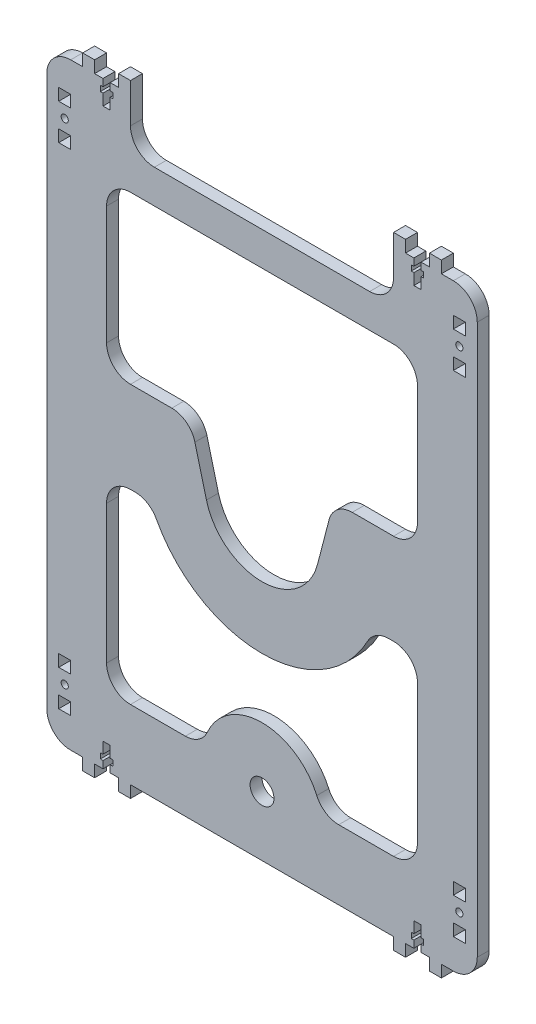
SolidWorks part; units mm, degrees
ref_plane "Front Plane" through (0, 0, 0) normal (0, 0, 1) x (1, 0, 0)
ref_plane "Top Plane" through (0, 0, 0) normal (0, 1, 0) x (1, 0, 0)
ref_plane "Right Plane" through (0, 0, 0) normal (1, 0, 0) x (0, 0, -1)
sketch "Sketch1" plane through (0, 0, 0) normal (0, 0, 1) x (1, 0, 0)
  line L0 (0, 0) -> (187.0096, 0) construction
  line L1 (-90, 125) -> (-55, 125) construction
  line L2 (-90, 125) -> (-90, -125)
  line L3 (-90, -125) -> (90, -125)
  line L4 (90, 125) -> (90, -125)
  line L5 (0, 0) -> (0, 134.5508) construction
  line L6 (-23.2273, -6.0409) -> (-30, 20)
  line L7 (-65, 89.5396) -> (65, 89.5396)
  line L8 (65, 89.5396) -> (65, 0) construction
  line L9 (65, 0) -> (-65, 0) construction
  line L10 (-65, 0) -> (-65, 89.5396) construction
  line L11 (-65, 0) -> (-20, 0) construction
  line L12 (20, 0) -> (65, 0) construction
  line L13 (82.5, 125) -> (82.5, -125) construction
  line L14 (0, 0) -> (0, -125) construction
  line L21 (-30, 20) -> (-65, 20)
  line L22 (-65, 20) -> (-65, 89.5396)
  line L23 (65, 20) -> (65, 89.5396)
  line L24 (30, 20) -> (65, 20)
  line L26 (-90, 125) -> (-55, 125)
  line L27 (23.2273, -6.0409) -> (30, 20)
  line L28 (-55, 125) -> (-55, 103.5988)
  line L29 (-55, 103.5988) -> (55, 103.5988)
  line L30 (55, 103.5988) -> (55, 125)
  line L31 (55, 125) -> (90, 125) construction
  line L32 (55, 125) -> (90, 125)
  line L33 (-46.616, -18.0816) -> (-65, -18.0816)
  line L34 (-65, -18.0816) -> (-65, -95.958)
  line L35 (-65, -95.958) -> (-24.6711, -95.958)
  line L36 (46.616, -18.0816) -> (65, -18.0816)
  line L37 (65, -18.0816) -> (65, -95.958)
  line L38 (65, -95.958) -> (24.6711, -95.958)
  circle A1 centre (0, -100) radius 5
  circle A2 centre (0, 0) radius 24 construction
  arc A3 (23.2273, -6.0409) -> (-23.2273, -6.0409) centre (0, 0) cw
  circle A4 centre (0, 0) radius 50 construction
  circle A5 centre (0, -100) radius 25 construction
  arc A6 (24.6711, -95.958) -> (-24.6711, -95.958) centre (0, -100) ccw
  arc A7 (-46.616, -18.0816) -> (46.616, -18.0816) centre (0, 0) ccw
  line B0 (82.5, 107.5) -> (82.5, 97.5) construction
  line B1 (80, 107.5) -> (80, 112.5)
  line B2 (80, 107.5) -> (85, 107.5)
  line B3 (85, 107.5) -> (85, 112.5)
  line B4 (80, 112.5) -> (85, 112.5)
  line B5 (80, 97.5) -> (80, 92.5)
  line B6 (80, 97.5) -> (85, 97.5)
  line B7 (85, 97.5) -> (85, 92.5)
  line B8 (80, 92.5) -> (85, 92.5)
  line B9 (82.5, 102.5) -> (75.5276, 102.5) construction
  circle B10 centre (82.5, 102.5) radius 1.5
  line B11 (82.5, -107.5) -> (82.5, -97.5) construction
  line B12 (80, -107.5) -> (80, -112.5)
  line B13 (80, -107.5) -> (85, -107.5)
  line B14 (85, -107.5) -> (85, -112.5)
  line B15 (80, -112.5) -> (85, -112.5)
  line B16 (80, -97.5) -> (80, -92.5)
  line B17 (80, -97.5) -> (85, -97.5)
  line B18 (85, -97.5) -> (85, -92.5)
  line B19 (80, -92.5) -> (85, -92.5)
  line B20 (82.5, -102.5) -> (75.5276, -102.5) construction
  circle B21 centre (82.5, -102.5) radius 1.5
  line B22 (-82.5, 107.5) -> (-82.5, 97.5) construction
  line B23 (-80, 107.5) -> (-80, 112.5)
  line B24 (-80, 107.5) -> (-85, 107.5)
  line B25 (-85, 107.5) -> (-85, 112.5)
  line B26 (-80, 112.5) -> (-85, 112.5)
  line B27 (-80, 97.5) -> (-80, 92.5)
  line B28 (-80, 97.5) -> (-85, 97.5)
  line B29 (-85, 97.5) -> (-85, 92.5)
  line B30 (-80, 92.5) -> (-85, 92.5)
  line B31 (-82.5, 102.5) -> (-75.5276, 102.5) construction
  circle B32 centre (-82.5, 102.5) radius 1.5
  line B33 (-82.5, -107.5) -> (-82.5, -97.5) construction
  line B34 (-80, -107.5) -> (-80, -112.5)
  line B35 (-80, -107.5) -> (-85, -107.5)
  line B36 (-85, -107.5) -> (-85, -112.5)
  line B37 (-80, -112.5) -> (-85, -112.5)
  line B38 (-80, -97.5) -> (-80, -92.5)
  line B39 (-80, -97.5) -> (-85, -97.5)
  line B40 (-85, -97.5) -> (-85, -92.5)
  line B41 (-80, -92.5) -> (-85, -92.5)
  line B42 (-82.5, -102.5) -> (-75.5276, -102.5) construction
  circle B43 centre (-82.5, -102.5) radius 1.5
  line B44 (-67.6, -122) -> (-67.6, -119.7)
  line B45 (-63.5, -119.7) -> (-63.5, -115)
  line B46 (-66.5, -115) -> (-66.5, -119.7)
  line B47 (-67.6, -119.7) -> (-66.5, -119.7)
  line B48 (-65, -125) -> (-65, -113.7792) construction
  line B49 (-66.5, -125) -> (-70, -125)
  line B50 (-70, -130) -> (-75, -130)
  line B51 (-75, -130) -> (-75, -125)
  line B52 (-70, -130) -> (-70, -125)
  line B53 (-63.5, -125) -> (-60, -125)
  line B54 (-60, -125) -> (-60, -130)
  line B55 (-60, -130) -> (-55, -130)
  line B56 (-55, -130) -> (-55, -125)
  line B57 (-66.5, -125) -> (-63.5, -125) construction
  line B58 (-63.5, -125) -> (-63.5, -122)
  line B59 (-63.5, -119.7) -> (-62.4, -119.7)
  line B60 (-62.4, -122) -> (-63.5, -122)
  line B61 (-63.5, -115) -> (-66.5, -115)
  line B62 (-66.5, -122) -> (-67.6, -122)
  line B63 (-62.4, -119.7) -> (-62.4, -122)
  line B64 (-66.5, -122) -> (-66.5, -125)
  line B65 (-65, -115) -> (-65, -125) construction
  line B66 (62.4, -122) -> (62.4, -119.7)
  line B67 (66.5, -119.7) -> (66.5, -115)
  line B68 (63.5, -115) -> (63.5, -119.7)
  line B69 (62.4, -119.7) -> (63.5, -119.7)
  line B70 (65, -125) -> (65, -113.7792) construction
  line B71 (63.5, -125) -> (60, -125)
  line B72 (60, -130) -> (55, -130)
  line B73 (55, -130) -> (55, -125)
  line B74 (60, -130) -> (60, -125)
  line B75 (66.5, -125) -> (70, -125)
  line B76 (70, -125) -> (70, -130)
  line B77 (70, -130) -> (75, -130)
  line B78 (75, -130) -> (75, -125)
  line B79 (63.5, -125) -> (66.5, -125) construction
  line B80 (66.5, -125) -> (66.5, -122)
  line B81 (66.5, -119.7) -> (67.6, -119.7)
  line B82 (67.6, -122) -> (66.5, -122)
  line B83 (66.5, -115) -> (63.5, -115)
  line B84 (63.5, -122) -> (62.4, -122)
  line B85 (67.6, -119.7) -> (67.6, -122)
  line B86 (63.5, -122) -> (63.5, -125)
  line B87 (65, -115) -> (65, -125) construction
  line B88 (67.6, 122) -> (67.6, 119.7)
  line B89 (63.5, 119.7) -> (63.5, 115)
  line B90 (66.5, 115) -> (66.5, 119.7)
  line B91 (67.6, 119.7) -> (66.5, 119.7)
  line B92 (65, 125) -> (65, 113.7792) construction
  line B93 (66.5, 125) -> (70, 125)
  line B94 (70, 130) -> (75, 130)
  line B95 (75, 130) -> (75, 125)
  line B96 (70, 130) -> (70, 125)
  line B97 (63.5, 125) -> (60, 125)
  line B98 (60, 125) -> (60, 130)
  line B99 (60, 130) -> (55, 130)
  line B100 (55, 130) -> (55, 125)
  line B101 (66.5, 125) -> (63.5, 125) construction
  line B102 (63.5, 125) -> (63.5, 122)
  line B103 (63.5, 119.7) -> (62.4, 119.7)
  line B104 (62.4, 122) -> (63.5, 122)
  line B105 (63.5, 115) -> (66.5, 115)
  line B106 (66.5, 122) -> (67.6, 122)
  line B107 (62.4, 119.7) -> (62.4, 122)
  line B108 (66.5, 122) -> (66.5, 125)
  line B109 (65, 115) -> (65, 125) construction
  line B110 (-62.4, 122) -> (-62.4, 119.7)
  line B111 (-66.5, 119.7) -> (-66.5, 115)
  line B112 (-63.5, 115) -> (-63.5, 119.7)
  line B113 (-62.4, 119.7) -> (-63.5, 119.7)
  line B114 (-65, 125) -> (-65, 113.7792) construction
  line B115 (-63.5, 125) -> (-60, 125)
  line B116 (-60, 130) -> (-55, 130)
  line B117 (-55, 130) -> (-55, 125)
  line B118 (-60, 130) -> (-60, 125)
  line B119 (-66.5, 125) -> (-70, 125)
  line B120 (-70, 125) -> (-70, 130)
  line B121 (-70, 130) -> (-75, 130)
  line B122 (-75, 130) -> (-75, 125)
  line B123 (-63.5, 125) -> (-66.5, 125) construction
  line B124 (-66.5, 125) -> (-66.5, 122)
  line B125 (-66.5, 119.7) -> (-67.6, 119.7)
  line B126 (-67.6, 122) -> (-66.5, 122)
  line B127 (-66.5, 115) -> (-63.5, 115)
  line B128 (-63.5, 122) -> (-62.4, 122)
  line B129 (-67.6, 119.7) -> (-67.6, 122)
  line B130 (-63.5, 122) -> (-63.5, 125)
  line B131 (-65, 115) -> (-65, 125) construction
  dimension "D8" = 50
  dimension "D10" = 10
  dimension "D2" = 24
  dimension "D13" = 100
  dimension "D3" = 250
  dimension "D4" = 180
  dimension "D5" = 35
  dimension "D6" = 25
  dimension "D7" = 20
  dimension "D9" = 22.5
  dimension "D11" = 25
  dimension "D12" = 7.5
sketch_block_instance "Trou M3 plots 5mm-7"
sketch_block "Trou M3 plots 5mm" parameters "D2"=3, "D1"=5, "D3"=5, "D4"=10
sketch_block_instance "Trou M3 plots 5mm-8"
sketch_block_instance "Trou M3 plots 5mm-9"
sketch_block_instance "Trou M3 plots 5mm-10"
sketch_block_instance "Insert M3 plots ep 5mm-1"
sketch_block "Insert M3 plots ep 5mm" parameters "D1"=10, "D2"=5, "D3"=5
sketch_block_instance "Decoupe Insert M3-4"
sketch_block "Decoupe Insert M3" parameters "D1"=5.2, "D2"=3, "D3"=2.3, "D4"=3, "D5"=10
sketch_block_instance "Insert M3 plots ep 5mm-2"
sketch_block_instance "Insert M3 plots ep 5mm-3"
sketch_block_instance "Insert M3 plots ep 5mm-5"
extrude "Boss-Extrude1" add sketch "Sketch1" along normal blind 5 contours B130 B128 B110 B113 B112 B127 B111 B125 B129 B126 B124 L26 L2 L3 B64 B62 B44 B47 B46 B61 B45 B59 B63 B60 B58 B86 B84 B66 B69 B68 B83 B67 B81 B85 B82 B80 L4 | B50 B52 L3 B51 | B55 B56 L3 B54 | B72 B74 L3 B73 | B77 B78 L3 B76 | B121 B122 L26 B120 | B116 B118 L26 B117 | B99 B100 L26 B98 | B94 B96 L26 B95 region at (-82.5, 121.9194, 0) region at (-72.5, 127.5, 0) region at (-72.5, -127.5, 0) region at (-57.5, 127.5, 0) region at (-57.5, -127.5, 0) region at (57.5, -127.5, 0) region at (57.5, 127.5, 0) region at (72.5, -127.5, 0) region at (72.5, 127.5, 0)
fillet "Fillet1" radius 10 20 edges at (-90, -125, 2.5) (90, -125, 2.5) (-90, 125, 2.5) (90, 125, 2.5) (-55, 103.5988, 2.5) (55, 103.5988, 2.5) (24.6711, -95.958, 2.5) (-24.6711, -95.958, 2.5) (-65, -95.958, 2.5) (65, -95.958, 2.5) (65, -18.0816, 2.5) (46.616, -18.0816, 2.5) (-46.616, -18.0816, 2.5) (-65, -18.0816, 2.5) (65, 89.5396, 2.5) (-65, 89.5396, 2.5) (65, 20, 2.5) (-65, 20, 2.5) (30, 20, 2.5) (-30, 20, 2.5)
